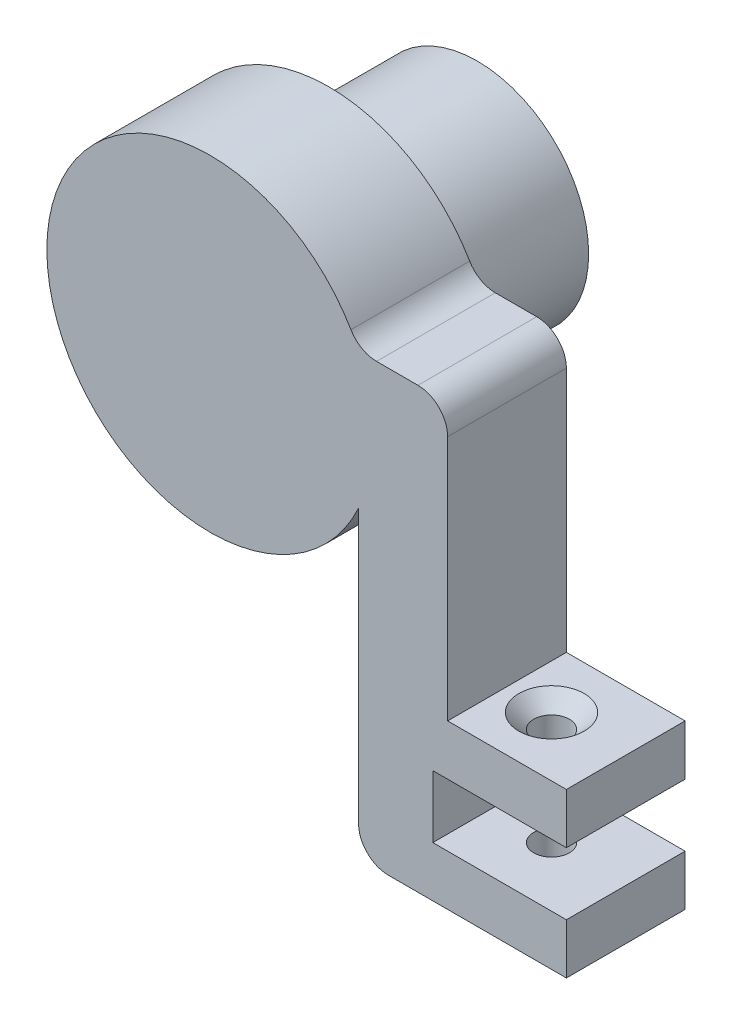
SolidWorks part; units mm, degrees
ref_plane "Plan de face" through (0, 0, 0) normal (0, 0, 1) x (1, 0, 0)
ref_plane "Plan de dessus" through (0, 0, 0) normal (0, 1, 0) x (1, 0, 0)
ref_plane "Plan de droite" through (0, 0, 0) normal (1, 0, 0) x (0, 0, -1)
sketch "Esquisse1" plane through (0, 0, 0) normal (0, 0, 1) x (1, 0, 0)
  line L1 (0, 0) -> (35, 0) construction
  line L2 (0, 0) -> (0, -36) construction
  line L3 (0, -36) -> (35, -36) construction
  line L4 (35, 0) -> (35, -36) construction
  line L5 (21, -6.4174) -> (27, -6.4174)
  line L7 (27, -6.4174) -> (27, -25)
  line L8 (35, -28.4) -> (35, -25)
  line L9 (35, -36) -> (21, -36)
  line L10 (35, -36) -> (35, -32.6)
  line L11 (35, -25) -> (27, -25)
  line L14 (21, -36) -> (21, -15.5826)
  line L17 (35, -32.6) -> (26, -32.6)
  line L19 (35, -28.4) -> (26, -28.4)
  line L20 (26, -32.6) -> (26, -28.4)
  line L21 (21, -6.4174) -> (21, -15.5826) construction
  arc A0 (21, -6.4174) -> (21, -15.5826) centre (11, -11) ccw
  point P6 (21, -11)
  point P20 (26, -30.5)
  dimension "D3" = 22
  dimension "D1" = 35
  dimension "D2" = 36
  dimension "D4" = 11
  dimension "D5" = 11
  dimension "D6" = 11
  dimension "D8" = 9
  dimension "D9" = 4.2
  dimension "D10" = 5.5
  dimension "D11" = 8
  dimension "D7" = 21
extrude "Boss.-Extru.1" add sketch "Esquisse1" along normal blind 8
sketch "Esquisse2" plane through (0, -25, 0) normal (0, 1, 0) x (1, 0, 0)
  line L0 (27, -8) -> (27, 0) construction
  line L1 (35, -8) -> (27, -8) construction
  circle A0 centre (30, -4) radius 1
  dimension "D1" = 2
  dimension "D2" = 3
  dimension "D3" = 4
extrude "Enlèv. mat.-Extru.1" cut sketch "Esquisse2" against normal up to surface (11 mm away) up to face at (28, -36, 4)
hole_wizard "Fraisage pour vis à tête fraisée M21" positions "Esquisse3" profile "Esquisse4" countersink size "M2" standard "ISO"
sketch "Esquisse3" plane through (0, -25, 0) normal (0, 1, 0) x (1, 0, 0)
  point P0 (30, -4)
sketch "Esquisse4" plane through (30, -25, 4) normal (1, 0, 0) x (0, 0, 1)
  line L0 (0, 0) -> (0, 11.721)
  line L1 (0, 11.721) -> (1.2, 11)
  line L2 (1.2, 11) -> (1.2, 1)
  line L3 (1.2, 1) -> (2.2, 0)
  line L5 (2.2, 0) -> (0, 0)
  line L6 (-1.2, 1) -> (-2.2, 0) construction
  line L10 (0, 11.721) -> (-1.2, 11) construction
  line L11 (0, -6.35) -> (0, 107.95) construction
  dimension "Diamètre du perçage" = 2.4
  dimension "Profondeur du perçage" = 11
  dimension "Diamètre du fraisage entrant" = 4.4
  dimension "Angle du fraisage entrant" = 90
  dimension "Angle de pointe" = 118
fillet "Congé1" radius 2 3 edges at (21, -36, 4) (21, -6.4174, 4) (27, -6.4174, 4)
sketch "Esquisse5" plane through (0, 0, 8) normal (0, 0, 1) x (1, 0, 0)
  circle A0 centre (11, -11) radius 7.5
  dimension "D1" = 15
extrude "Boss.-Extru.2" [suppressed] add sketch "Esquisse5" along normal blind 10
sketch "Esquisse6" plane through (0, 0, 0) normal (0, 0, -1) x (-1, 0, 0)
  circle A0 centre (-11, -11) radius 7.5
  dimension "D1" = 15
extrude "Boss.-Extru.3" add sketch "Esquisse6" along normal blind 10
equation "\"D4@Esquisse1\"=\"D3@Esquisse1\"/2"
equation "\"D5@Esquisse1\"=\"D3@Esquisse1\"/2"
equation "\"D10@Esquisse1\"=\"D6@Esquisse1\"/2"
